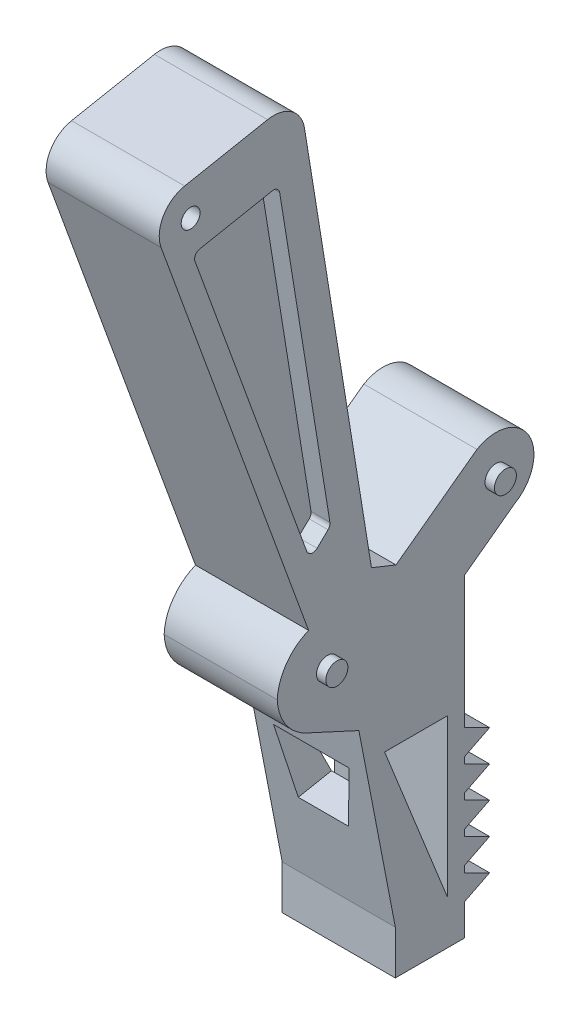
SolidWorks part; units mm, degrees
ref_plane "Front Plane" through (0, 0, 0) normal (0, 0, 1) x (1, 0, 0)
ref_plane "Top Plane" through (0, 0, 0) normal (0, 1, 0) x (1, 0, 0)
ref_plane "Right Plane" through (0, 0, 0) normal (1, 0, 0) x (0, 0, -1)
sketch "Sketch1" plane through (0, 0, 0) normal (1, 0, 0) x (0, 0, -1)
  line L0 (129.6365, 390.8123) -> (437.258, 390.8123) construction
  line L1 (0, 0) -> (-25.4779, 70)
  line L2 (-25.4779, 70) -> (-1.4779, 74.6397)
  line L3 (-1.4779, 74.6397) -> (10, 3.6397)
  line L4 (10, 3.6397) -> (0, 0)
  line L5 (-5, -1.8199) -> (-5, -11.8199)
  line L6 (-5, -11.8199) -> (8, -17.805)
  line L7 (8, -17.805) -> (13.7996, -47.805)
  line L8 (13.7996, -47.805) -> (13.7996, -54.805)
  line L9 (13.7996, -54.805) -> (24.7996, -54.805)
  line L10 (24.7996, -54.805) -> (24.7996, -4.805)
  line L11 (24.7996, -4.805) -> (32.8534, 1.1226)
  line L12 (0, 0) -> (-5, -1.8199)
  line L13 (10, 3.6397) -> (13.9014, 2.0737)
  line L14 (13.9014, 2.0737) -> (26.7874, 11.5579)
  line L15 (32.8534, 1.1226) -> (26.7874, 11.5579) construction
  line L16 (0, 0) -> (-44.3079, 0) construction
  arc A0 (32.8534, 1.1226) -> (26.7874, 11.5579) centre (29.8204, 6.3403) ccw
  dimension "D1" = 70
  dimension "D2" = 24
  dimension "D3" = 71
  dimension "D4" = 10
  dimension "D5" = 5
  dimension "D6" = 10
  dimension "D7" = 13
  dimension "D8" = 30
  dimension "D9" = 7
  dimension "D10" = 11
  dimension "D11" = 50
  dimension "D12" = 10
  dimension "D13" = 12
  dimension "D14" = 70
  dimension "D15" = 16
extrude "Boss-Extrude1" add sketch "Sketch1" along normal blind 18 contours L11 A0 L14 L13 L4 L12 L5 L6 L7 L8 L9 L10 | L4 L3 L2 L1 region at (0, 41.6919, 5.4988) region at (0, -16.8385, -16.2928)
sketch "Sketch2" plane through (18, 0, 0) normal (1, 0, 0) x (0, 0, -1)
  line L0 (12.0939, -22.805) -> (22.0939, -22.805)
  line L1 (22.0939, -22.805) -> (22.0939, -47.805)
  line L2 (22.0939, -47.805) -> (12.0939, -22.805)
  line L3 (13.7996, -47.805) -> (22.0939, -47.805) construction
  dimension "D1" = 25
  dimension "D2" = 10
extrude "Cut-Extrude1" cut sketch "Sketch2" against normal blind 18
sketch "Sketch3" plane through (18, 0, 0) normal (1, 0, 0) x (0, 0, -1)
  line L0 (24.7996, -49.805) -> (28.7996, -47.805)
  line L1 (28.7996, -47.805) -> (24.7996, -47.805)
  line L2 (24.7996, -54.805) -> (24.7996, -4.805) construction
  line L3 (24.7996, -49.805) -> (24.7996, -47.805)
  line L4 (24.7996, -45.805) -> (28.7996, -47.805)
  line L5 (24.7996, -45.805) -> (24.7996, -47.805)
  line L6 (13.7996, -54.805) -> (24.7996, -54.805) construction
  line M21 (24.7996, -54.805) -> (24.7996, -4.805)
  dimension "D1" = 5
  dimension "D2" = 4
  dimension "D3" = 2
  dimension "D4" = 2
extrude "Boss-Extrude2" add sketch "Sketch3" against normal blind 18 contours L0 L1 M21 | L4 L1 M21 region at (18, -48.4716, -26.133) region at (18, -47.1383, -26.133)
pattern_linear "LPattern1" count 5 spacing 5 along (0, 1, 0) of "Boss-Extrude2"
fillet "Fillet1" radius 8 2 edges at (9, -1.8199, 5) (9, -11.8199, 5)
fillet "Fillet2" radius 5 2 edges at (9, 74.6397, 1.4779) (9, 70, 25.4779)
sketch "Sketch4" plane through (18, 0, 0) normal (1, 0, 0) x (0, 0, -1)
  circle A0 centre (-18.7751, 66.2032) radius 1.5
  dimension "D1" = 3
extrude "Cut-Extrude2" cut sketch "Sketch4" against normal blind 18
sketch "Sketch5" plane through (0, 0.8494, -4.3937) normal (0, -0.1898, 0.9818) x (1, 0, 0)
  line L0 (9, -49.5552) -> (9, -18.9998) construction
  line L1 (18, -49.5552) -> (0, -49.5552) construction
  line L2 (18, -18.9998) -> (0, -18.9998) construction
  line L3 (15, -26.4998) -> (9, -26.4998)
  line L4 (9, -26.4998) -> (3, -26.4998)
  line L5 (3, -26.4998) -> (5, -36.6919)
  line L6 (5, -36.6919) -> (9, -36.6919)
  line L7 (9, -36.6919) -> (13, -36.6919)
  line L8 (13, -36.6919) -> (15, -26.4998)
  line L9 (18, -18.9998) -> (18, -49.5552) construction
  line L10 (0, -58.5158) -> (0, -9.4248) construction
  dimension "D1" = 4
  dimension "D2" = 4
  dimension "D3" = 3
  dimension "D4" = 3
  dimension "D5" = 7.5
extrude "Cut-Extrude3" cut sketch "Sketch5" against normal blind 6
sketch "Sketch6" plane through (18, 0, 0) normal (1, 0, 0) x (0, 0, -1)
  circle A0 centre (29.8204, 6.3403) radius 1.75
  dimension "D1" = 3.5
extrude "Boss-Extrude3" add sketch "Sketch6" along normal blind 1.5
sketch "Sketch7" plane through (18, 0, 0) normal (1, 0, 0) x (0, 0, -1)
  circle A0 centre (3, -6.6959) radius 1.75
  dimension "D1" = 3.5
extrude "Boss-Extrude4" add sketch "Sketch7" along normal blind 1.5
sketch "Sketch8" plane through (18, 0, 0) normal (1, 0, 0) x (0, 0, -1)
  line L0 (-17.3327, 61.2387) -> (-5.7815, 63.4718)
  line L1 (-4.6045, 62.6495) -> (3.3883, 13.2079)
  line L2 (3.0943, 12.3276) -> (1.345, 10.6453)
  line L3 (-0.2878, 11.0241) -> (-18.0826, 59.9148)
  line L4 (0, 0) -> (-25.4779, 70) construction
  line L5 (-1.4779, 74.6397) -> (10, 3.6397) construction
  line L9 (-25.4779, 70) -> (-1.4779, 74.6397) construction
  arc A0 (-17.3327, 61.2387) -> (-18.0826, 59.9148) centre (-17.1429, 60.2569) ccw
  arc A1 (-4.6045, 62.6495) -> (-5.7815, 63.4718) centre (-5.5917, 62.4899) ccw
  arc A2 (1.345, 10.6453) -> (-0.2878, 11.0241) centre (0.6519, 11.3661) cw
  arc A3 (3.3883, 13.2079) -> (3.0943, 12.3276) centre (2.4011, 13.0484) cw
  dimension "D3" = 1
  dimension "D4" = 1
  dimension "D5" = 1
  dimension "D6" = 1
  dimension "D1" = 3.5
  dimension "D2" = 5
extrude "Cut-Extrude4" cut sketch "Sketch8" against normal blind 3
ref_plane "Plane1" through (9, 0, 0) normal (1, 0, 0) x (0, 0, -1)
mirror "Mirror1" about plane through (9, 0, 0) normal (1, 0, 0) of "Boss-Extrude4", "Boss-Extrude3", "Cut-Extrude4"
